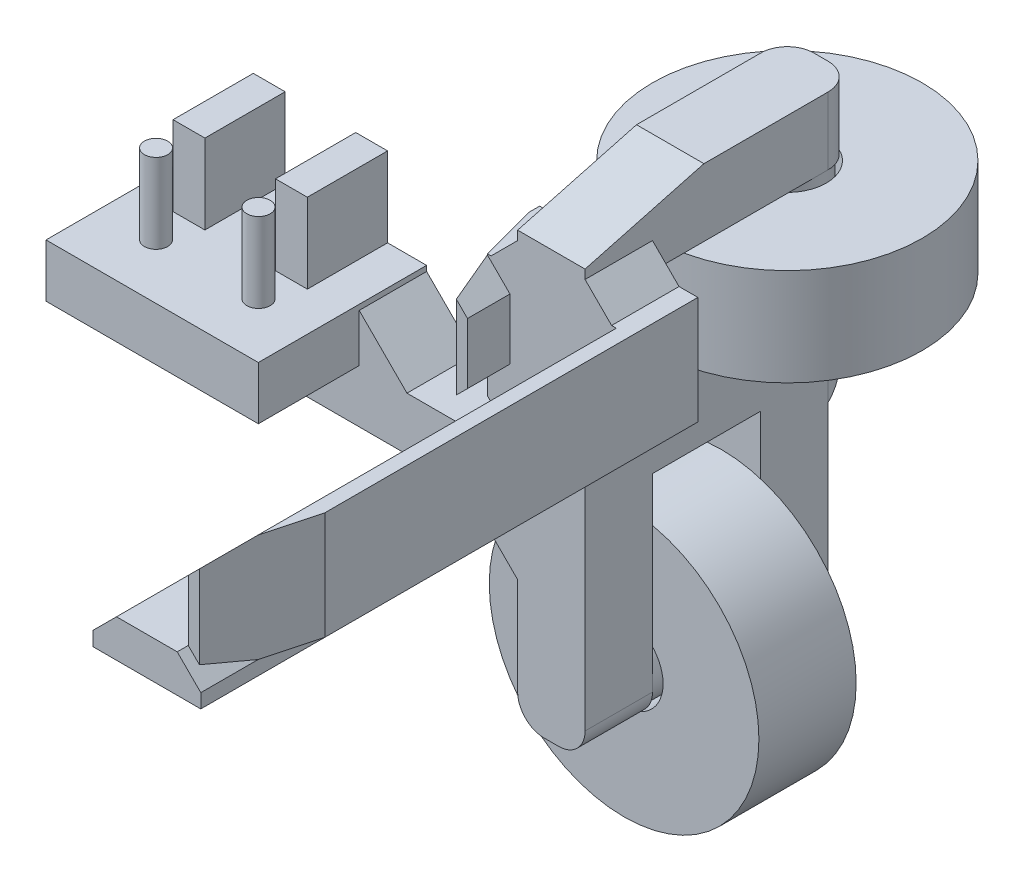
SolidWorks part; units mm, degrees
ref_plane "Front Plane" through (0, 0, 0) normal (0, 0, 1) x (1, 0, 0)
ref_plane "Top Plane" through (0, 0, 0) normal (0, 1, 0) x (1, 0, 0)
ref_plane "Right Plane" through (0, 0, 0) normal (1, 0, 0) x (0, 0, -1)
sketch "Sketch1" plane through (0, 0, 0) normal (0, 0, 1) x (1, 0, 0)
  line L1 (6.12, -5.08) -> (3.9, -2.86)
  line L2 (3.9, -2.86) -> (3.9, 2.86)
  line L3 (3.9, 2.86) -> (6.12, 5.08)
  line L5 (-6.12, -5.08) -> (-3.9, -2.86)
  line L6 (-3.9, -2.86) -> (-3.9, 2.86)
  line L7 (-3.9, 2.86) -> (-6.12, 5.08)
  line L8 (3.9, 0) -> (-3.9, 0) construction
  line L9 (0, 0) -> (-8.3021, -8.3021) construction
  line L10 (-6.12, 5.08) -> (-7.45, 5.08)
  line L12 (-6.12, -5.08) -> (-7.45, -5.08)
  line L13 (-7.45, 5.08) -> (-7.45, -5.08)
  line L14 (6.12, -5.08) -> (7.45, -5.08)
  line L16 (6.12, 5.08) -> (7.45, 5.08)
  line L17 (7.45, -5.08) -> (7.45, 5.08)
  line L18 (5.08, -7.45) -> (-5.08, -7.45)
  line L19 (-5.08, -6.12) -> (-5.08, -7.45)
  line L20 (5.08, -6.12) -> (5.08, -7.45)
  line L21 (2.86, -3.9) -> (5.08, -6.12)
  line L22 (-2.86, -3.9) -> (2.86, -3.9)
  line L23 (-5.08, -6.12) -> (-2.86, -3.9)
  dimension "D1" = 45
  dimension "D2" = 10.16
  dimension "D3" = 5.72
  dimension "D5" = 7.8
  dimension "D6" = 1.33
  dimension "D7" = 45
extrude "Boss-Extrude1" add sketch "Sketch1" along normal blind 38.1
chamfer "Chamfer1" distance 2.5 angle 75 1 edges at (7.45, 0, 38.1) first distance on face at (5.8233, 0, 38.1)
chamfer "Chamfer2" distance 2.5 angle 75 1 edges at (-7.45, 0, 38.1) first distance on face at (-5.8233, 0, 38.1)
sketch "Sketch3" plane through (0, 0, 0) normal (0, 0, 1) x (1, 0, 0)
  line L0 (-7.45, -5.08) -> (-6.12, -5.08) construction
  line L1 (7.45, 5.08) -> (-7.45, 5.08)
  line L2 (7.45, 5.08) -> (7.45, -5.08)
  line L4 (-7.45, 5.08) -> (-7.45, -5.08)
  line L5 (-6.12, 5.08) -> (-7.45, 5.08) construction
  line L6 (-7.45, 5.08) -> (-7.45, -5.08) construction
  line L7 (7.45, -5.08) -> (5.08, -7.45)
  line L8 (5.08, -7.45) -> (-5.08, -7.45)
  line L9 (-5.08, -7.45) -> (-7.45, -5.08)
extrude "Boss-Extrude2" add sketch "Sketch3" against normal blind 6.35
sketch "Sketch4" plane through (0, 0, -6.35) normal (0, 0, -1) x (-1, 0, 0)
  line L0 (-3.175, 5.08) -> (3.175, 5.08)
  line L5 (-3.175, -11.43) -> (3.175, -11.43)
  line L6 (-3.175, -11.43) -> (-3.175, -5.08)
  line L7 (-3.175, 11.43) -> (3.175, 11.43)
  line L8 (3.175, -11.43) -> (3.175, -5.08)
  line L11 (-7.45, 5.08) -> (7.45, 5.08) construction
  line L12 (-3.175, -5.08) -> (3.175, -5.08)
  line L14 (-3.175, 5.08) -> (-3.175, 11.43)
  line L17 (3.175, 5.08) -> (3.175, 11.43)
  point P0 (0, 0)
  point P14 (0, 5.08)
  dimension "D1" = 6.35
extrude "Boss-Extrude3" add sketch "Sketch4" along normal blind 25.4 from surface starting at face at (0, -2.0883, 0)
sketch "Sketch5" plane through (0, -5.08, 0) normal (0, 1, 0) x (1, 0, 0)
  line L0 (-3.175, 25.4) -> (3.175, 25.4) construction
  line L1 (-3.175, 25.4) -> (-3.175, 0) construction
  line L2 (3.175, 25.4) -> (3.175, 0) construction
  circle A0 centre (0, 22.225) radius 3.175
extrude "Boss-Extrude4" add sketch "Sketch5" along normal up to next
sketch "Sketch6" plane through (0, -5.08, 0) normal (0, 1, 0) x (1, 0, 0)
  arc A1 (-3.175, 22.225) -> (3.175, 22.225) centre (0, 22.225) ccw construction
  circle A2 centre (0, 22.225) radius 12.7
  arc A3 (-3.175, 22.225) -> (3.175, 22.225) centre (0, 22.225) ccw construction
  circle A4 centre (0, 22.225) radius 3.675
  dimension "D1" = 0.5
  dimension "D2" = 25.4
extrude "Boss-Extrude5" add sketch "Sketch6" along normal blind 9.16 from offset 0.5
sketch "Sketch7" plane through (3.175, 0, 0) normal (1, 0, 0) x (0, 0, -1)
  line L0 (25.4, -11.43) -> (0, -11.43) construction
  line L1 (0, -11.43) -> (6.35, -11.43)
  line L2 (0, -11.43) -> (0, -31.75)
  line L3 (0, -31.75) -> (6.35, -31.75)
  line L4 (6.35, -11.43) -> (6.35, -31.75)
  line L5 (16.51, -11.43) -> (22.86, -11.43)
  line L6 (16.51, -11.43) -> (16.51, -31.75)
  line L7 (16.51, -31.75) -> (22.86, -31.75)
  line L8 (22.86, -11.43) -> (22.86, -31.75)
  line L9 (6.35, -11.43) -> (16.51, -11.43) construction
  line L10 (6.35, -5.08) -> (6.35, 5.08) construction
  dimension "D1" = 6.35
  dimension "D2" = 31.75
extrude "Boss-Extrude6" add sketch "Sketch7" against normal up to surface (6.35 mm away) up to face at (-3.175, -7.5714, -12.2464)
sketch "Sketch8" plane through (0, 0, -16.51) normal (0, 0, 1) x (1, 0, 0)
  line L0 (3.175, -7.45) -> (3.175, -31.75) construction
  line L1 (-3.175, -31.75) -> (-3.175, -7.45) construction
  line L2 (-3.175, -31.75) -> (3.175, -31.75) construction
  circle A0 centre (0, -28.575) radius 3.175
extrude "Boss-Extrude7" add sketch "Sketch8" along normal up to next
sketch "Sketch9" plane through (0, 0, -16.51) normal (0, 0, 1) x (1, 0, 0)
  circle A0 centre (0, -28.575) radius 3.675
  circle A1 centre (0, -28.575) radius 12.7
  arc A2 (3.175, -28.575) -> (-3.175, -28.575) centre (0, -28.575) ccw construction
  arc A3 (3.175, -28.575) -> (-3.175, -28.575) centre (0, -28.575) ccw construction
  dimension "D1" = 0.5
  dimension "D2" = 25.4
extrude "Boss-Extrude8" add sketch "Sketch9" along normal blind 9.16 from offset 0.5 separate body
chamfer "Chamfer3" distance 2.5 angle 45 3 edges at (3.175, 5.08, -3.175) (-3.175, 5.08, -3.175) (0, -11.43, -22.86)
fillet "Fillet1" radius 2.5 8 edges at (-3.175, -8.255, -25.4) (3.175, -8.255, -25.4) (-3.175, 8.255, -25.4) (3.175, 8.255, -25.4) (-3.175, -31.75, -3.175) (3.175, -31.75, -3.175) (-3.175, -31.75, -19.685) (3.175, -31.75, -19.685)
chamfer "Chamfer4" distance 3 angle 75 1 edges at (0, 11.43, 0) first distance on face at (0, -4.784, 0)
sketch "Sketch10" plane through (-7.45, 0, 0) normal (-1, 0, 0) x (0, 0, 1)
  line L1 (4, 5.08) -> (38.1, 5.08)
  line L2 (4, 5.08) -> (4, -5.08)
  line L3 (4, -5.08) -> (38.1, -5.08)
  line L4 (38.1, 5.08) -> (38.1, -5.08)
  line L5 (33.7335, -5.08) -> (28.7699, -5.08) construction
  line L6 (-6.35, 5.08) -> (28.7699, 5.08) construction
  line L7 (0, 7.58) -> (0, 5.08) construction
  point P5 (0, 0)
  point P6 (0, 0)
  point P9 (2.8469, 5.08)
  dimension "D1" = 4
extrude "Cut-Extrude1" cut sketch "Sketch10" against normal up to next (3.55 mm away)
chamfer "Chamfer5" distance 2.5 angle 75 1 edges at (-7.45, 0, 4) first distance on face at (-5.8233, 0, 4)
sketch "Sketch11" plane through (0, 0, 0) normal (0, 0, 1) x (1, 0, 0)
  line L0 (-3.175, -10.08) -> (-18.1, -10.08)
  line L1 (-3.175, -29.25) -> (-3.175, -7.45) construction
  line L2 (-18.1, -10.08) -> (-18.1, -5.08)
  line L3 (-18.1, -5.08) -> (-38.1, -5.08)
  line L4 (-38.1, -5.08) -> (-38.1, -15.08)
  line L5 (-38.1, -15.08) -> (-3.175, -15.08)
  line L6 (-3.175, -15.08) -> (-3.175, -10.08)
  line L8 (-38.1, -15.08) -> (-28.1, -15.08)
  line L9 (-38.1, -15.08) -> (-38.1, -10.08)
  line L10 (-38.1, -10.08) -> (-28.1, -10.08)
  line L11 (-28.1, -15.08) -> (-28.1, -10.08)
  line M15 (-3.175, -7.45) -> (-3.175, -29.25)
  dimension "D1" = 34.925
  dimension "D2" = 20
  dimension "D3" = 5
  dimension "D4" = 5
  dimension "D5" = 10
extrude "Boss-Extrude9" add sketch "Sketch11" against normal up to surface (6.35 mm away) contours L11 L5 L0 L2 L3 L4 L10 M15 region at (-21.1856, -10.3541, 0) up to face at (0, -19.2087, -6.35)
chamfer "Chamfer6" distance 5 angle 45 1 edges at (-3.175, -15.08, -3.175)
chamfer "Chamfer7" distance 4.5 angle 45 3 edges at (-3.175, -10.08, -3.175) (-18.1, -10.08, -3.175) (-28.1, -15.08, -3.175)
sketch "Sketch12" plane through (-38.1, 0, 0) normal (-1, 0, 0) x (0, 0, 1)
  line L0 (-6.35, -10.08) -> (0, -10.08) construction
  line L1 (0, -5.08) -> (9.5, -5.08)
  line L2 (0, -5.08) -> (0, -10.08)
  line L3 (0, -10.08) -> (9.5, -10.08)
  line L4 (9.5, -5.08) -> (9.5, -10.08)
  dimension "D1" = 9.5
extrude "Boss-Extrude10" add sketch "Sketch12" against normal up to surface (20 mm away) up to face at (-18.1, -5.33, -3.175)
sketch "Sketch13" plane through (0, -5.08, 0) normal (0, 1, 0) x (1, 0, 0)
  line L0 (-39.6357, -13.208) -> (-16.9436, -13.208) construction
  line L1 (-34.425, 6.35) -> (-31.425, 6.35)
  line L2 (-34.425, 6.35) -> (-34.425, -1.208)
  line L3 (-34.425, -1.208) -> (-31.425, -1.208)
  line L4 (-31.425, 6.35) -> (-31.425, -1.208)
  line L5 (-24.775, 6.35) -> (-21.775, 6.35)
  line L6 (-24.775, 6.35) -> (-24.775, -1.208)
  line L7 (-24.775, -1.208) -> (-21.775, -1.208)
  line L8 (-21.775, 6.35) -> (-21.775, -1.208)
  line L9 (-13.6, 0) -> (-18.1, 0) construction
  line L10 (-32.925, -4.308) -> (-23.275, -4.308) construction
  line L11 (-18.1, -9.5) -> (-38.1, -9.5) construction
  line L12 (-18.1, 6.35) -> (-38.1, 6.35) construction
  circle A0 centre (-32.925, -4.308) radius 1.1
  circle A1 centre (-23.275, -4.308) radius 1.1
  point P12 (-23.275, -1.208)
  point P13 (-32.925, -1.208)
  point P18 (-28.1, -9.5)
  point P21 (-28.1, -4.308)
  dimension "D1" = 2.2
  dimension "D2" = 3
  dimension "D3" = 3.1
  dimension "D4" = 9.65
  dimension "D5" = 12
  dimension "D6" = 13.208
extrude "Boss-Extrude11" add sketch "Sketch13" along normal blind 7.5
